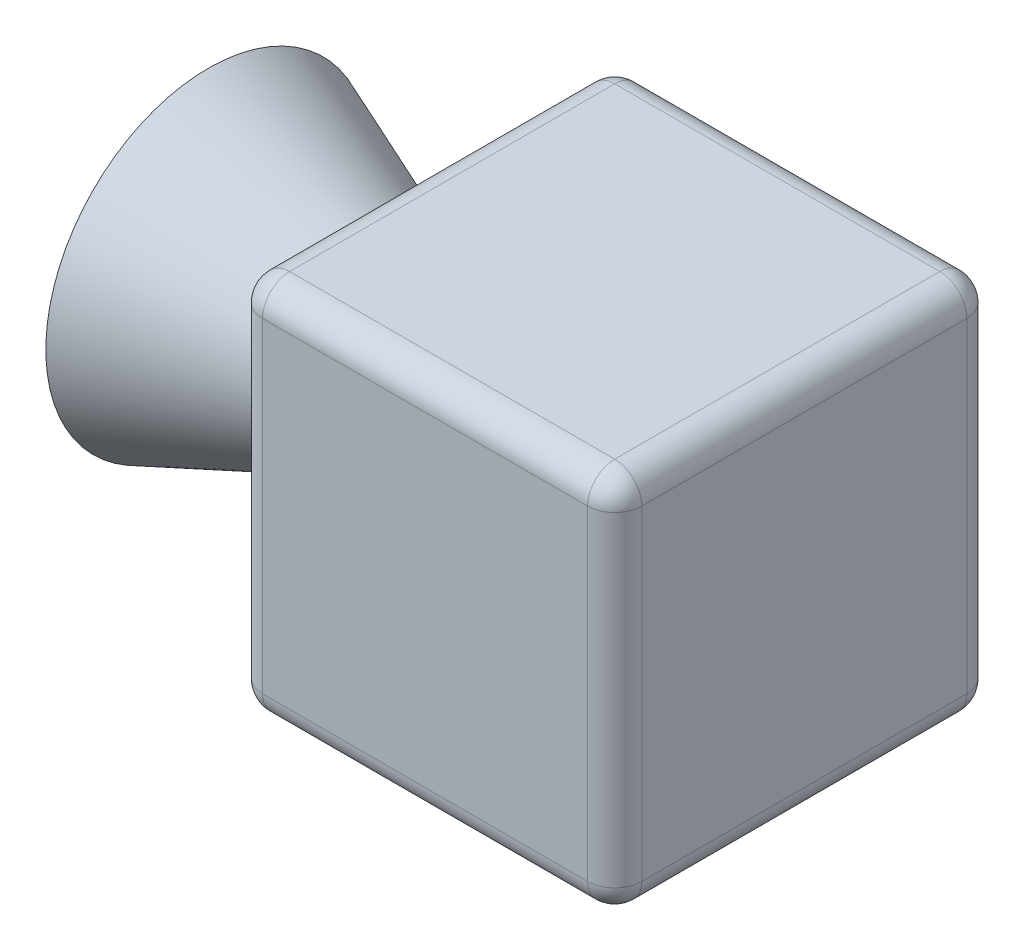
SolidWorks part; units mm, degrees
ref_plane "Ebene vorne" through (0, 0, 0) normal (0, 0, 1) x (1, 0, 0)
ref_plane "Ebene oben" through (0, 0, 0) normal (0, 1, 0) x (1, 0, 0)
ref_plane "Ebene rechts" through (0, 0, 0) normal (1, 0, 0) x (0, 0, -1)
sketch "Skizze1" plane through (0, 0, 0) normal (0, 1, 0) x (1, 0, 0)
  line L0 (-7, 2.8) -> (-15, 6)
  line L2 (-7, 0) -> (-7, 7)
  line L3 (-7, 7) -> (7, 7)
  line L4 (7, 0) -> (7, 7)
  line L5 (0, 0) -> (7, 7) construction
  line L6 (-7, 7) -> (0, 0) construction
  line L11 (-7.7191, 0) -> (-16.7318, 0) construction
  line L12 (7, 0) -> (0, 0) construction
  line L13 (-17, 0) -> (-7, 0)
  line L15 (-7, 0) -> (-7, -7)
  line L16 (-7, -7) -> (7, -7)
  line L17 (7, -7) -> (7, 0)
  line L18 (-7, 2.8) -> (-7, 0)
  arc A4 (-15, 6) -> (-17, 0) centre (-7, 0) ccw
  point P0 (0, 0)
  point P6 (3.5, 3.5)
  dimension "D3" = 6
  dimension "D1" = 14
  dimension "D2" = 10
revolve "Rotation1" add sketch "Skizze1" angle 360 about L11 region at (-12.2995, 0, -2.2944)
extrude "Aufsatz-Linear austragen2" add sketch "Skizze1<3>" along normal mid plane 14 contours L16 L17 L4 L3 L2 L15 region at (0, 0, 0)
sketch "Skizze1<3>" plane through (0, 0, 0) normal (0, 1, 0) x (1, 0, 0) same geometry as "Skizze1"
fillet "Verrundung2" radius 1 12 edges at (-7, 7, 0) (7, 7, 0) (7, -7, 0) (-7, -7, 0) (-7, 0, 7) (0, 7, 7) (7, 0, 7) (0, -7, 7) (7, 0, -7) (0, 7, -7) (-7, 0, -7) (0, -7, -7)
